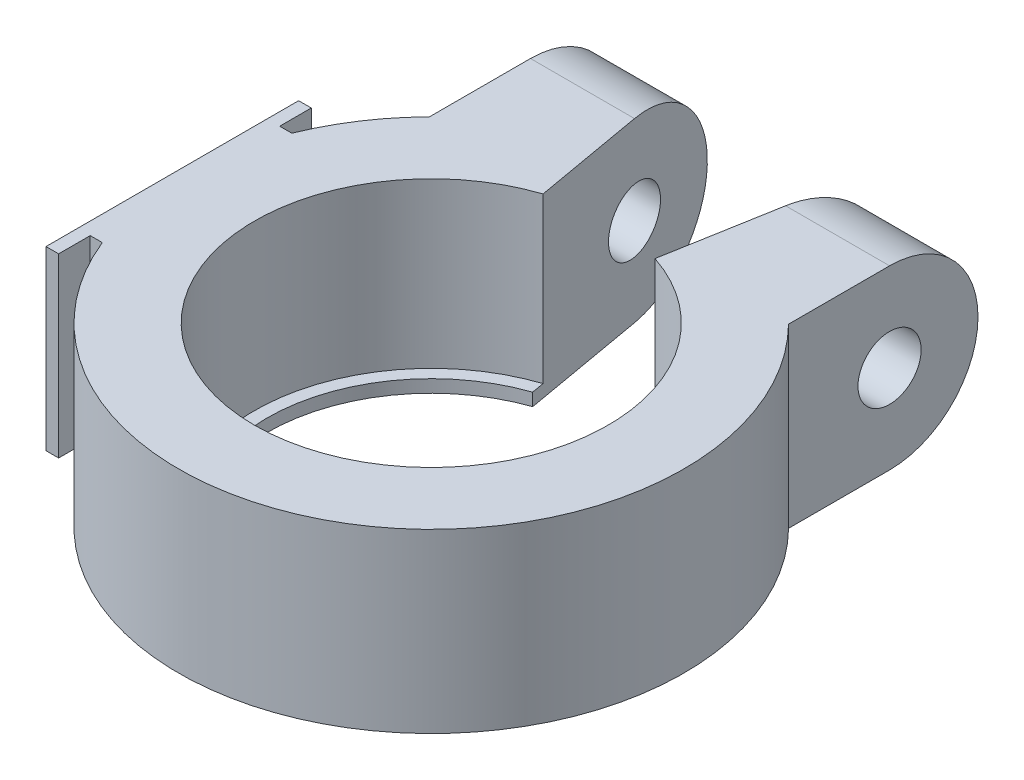
SolidWorks part; units mm, degrees
material "1023 Carbon Steel Sheet (SS)"
ref_plane "Front Plane" through (0, 0, 0) normal (0, 0, 1) x (1, 0, 0)
ref_plane "Top Plane" through (0, 0, 0) normal (0, 1, 0) x (1, 0, 0)
ref_plane "Right Plane" through (0, 0, 0) normal (1, 0, 0) x (0, 0, -1)
sketch "Sketch1" plane through (0, 0, 0) normal (0, 1, 0) x (1, 0, 0)
  line L0 (0, 0) -> (0, 85.0121) construction
  line L1 (-4.2544, 12.2841) -> (-7.2141, 29.0698)
  line L2 (4.2544, 12.2841) -> (7.2141, 29.0698)
  line L3 (7.2141, 29.0698) -> (14.2141, 29.0698)
  line L4 (14.2141, 29.0698) -> (14.2141, 14.0698)
  line L5 (-7.2141, 29.0698) -> (-14.2141, 29.0698)
  line L6 (-14.2141, 29.0698) -> (-14.2141, 14.0698)
  line L7 (0, 0) -> (-20, 0) construction
  line L8 (-19.5, -10) -> (-19.5, -7.5)
  line L9 (-19.5, 10) -> (-20.5, 10)
  line L10 (-19.5, -10) -> (-20.5, -10)
  line L11 (-20.5, 10) -> (-20.5, -10)
  line L12 (-19.5, 7.5) -> (-18.5405, 7.5)
  line L13 (-19.5, -7.5) -> (-18.5405, -7.5)
  line L14 (-19.5, 7.5) -> (-19.5, 10)
  arc A0 (-4.2544, 12.2841) -> (4.2544, 12.2841) centre (0, 0) ccw
  arc A1 (-14.2141, 14.0698) -> (-18.5405, 7.5) centre (0, 0) ccw
  arc A2 (-18.5405, -7.5) -> (14.2141, 14.0698) centre (0, 0) ccw
  point P16 (-20.5, 0)
  dimension "D2" = 40
  dimension "D8" = 13
  dimension "D3" = 15
  dimension "D4" = 7
  dimension "D5" = 10
  dimension "D6" = 10
  dimension "D7" = 7
  dimension "D9" = 8.5088
  dimension "D10" = 20
  dimension "D11" = 1
  dimension "D12" = 15
  dimension "D13" = 0.5
extrude "Boss-Extrude1" add sketch "Sketch1" along normal blind 14
fillet "Fillet1" 2 edges at (10.7141, 14, -29.0698) (10.7141, 0, -29.0698) type full round first side face at (-8.9528, 14, -7.7456) second side face at (-8.9528, 0, -7.7456) middle face at (10.7141, 7, -29.0698)
fillet "Fillet2" 2 edges at (-10.7141, 14, -29.0698) (-10.7141, 0, -29.0698) type full round first side face at (-9.0299, 14, -6.8706) second side face at (-9.0299, 0, -6.8706) middle face at (-10.7141, 7, -29.0698)
sketch "Sketch3" plane through (-14.2141, 0, 0) normal (-1, 0, 0) x (0, 0, 1)
  circle A0 centre (-22.0698, 7) radius 2.5
  dimension "D1" = 5
extrude "Cut-Extrude1" cut sketch "Sketch3" against normal through all contours A0
sketch "Sketch4" plane through (0, 14, 0) normal (0, 1, 0) x (1, 0, 0)
  circle A0 centre (0, 0) radius 14
  dimension "D1" = 28
extrude "Cut-Extrude2" cut sketch "Sketch4" against normal blind 13
